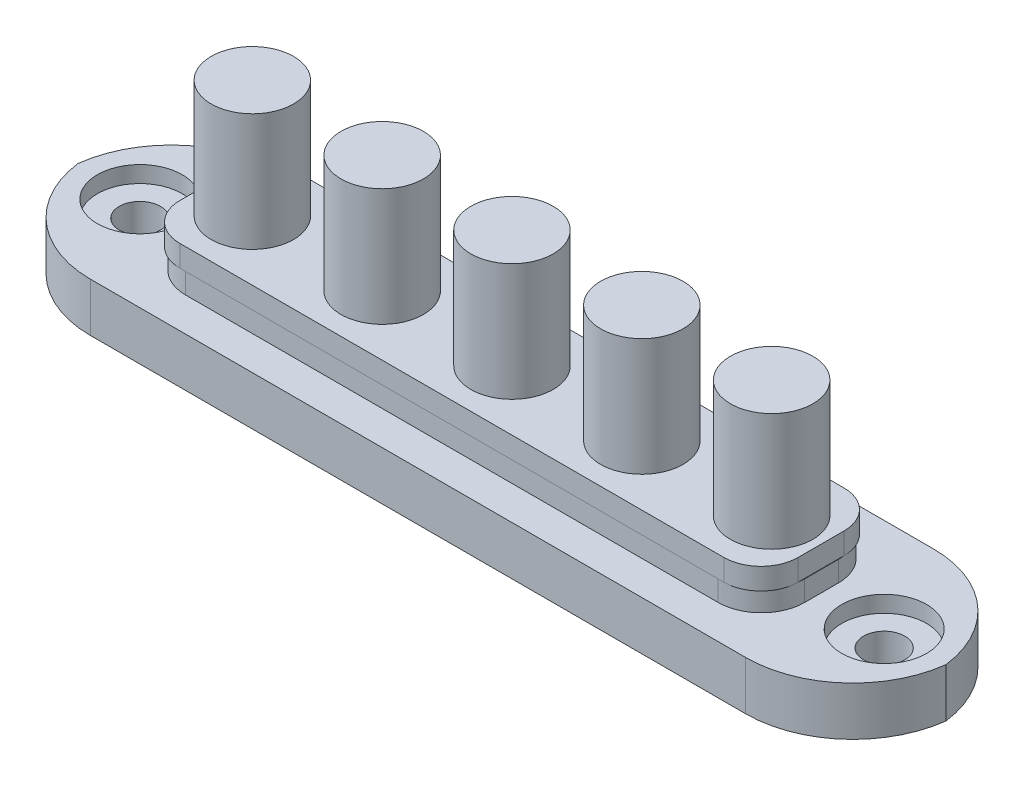
SolidWorks part; units mm, degrees
ref_plane "Front Plane" through (0, 0, 0) normal (0, 0, 1) x (1, 0, 0)
ref_plane "Top Plane" through (0, 0, 0) normal (0, 1, 0) x (1, 0, 0)
ref_plane "Right Plane" through (0, 0, 0) normal (1, 0, 0) x (0, 0, -1)
sketch "Sketch1" plane through (0, 0, 0) normal (0, 1, 0) x (1, 0, 0)
  line L1 (52.75, -11.4) -> (-52.75, -11.4)
  line L2 (52.75, -11.4) -> (52.75, 11.4)
  line L3 (52.75, 11.4) -> (-52.75, 11.4)
  line L4 (-52.75, -11.4) -> (-52.75, 11.4)
  line L5 (52.75, -11.4) -> (-52.75, 11.4) construction
  line L6 (52.75, 11.4) -> (-52.75, -11.4) construction
  point P0 (0, 0)
  dimension "D1" = 105.5
  dimension "D2" = 22.8
extrude "Boss-Extrude1" add sketch "Sketch1" along normal mid plane 5.92
fillet "Fillet1" radius 13 4 edges at (-52.75, 0, -11.4) (-52.75, 0, 11.4) (52.75, 0, -11.4) (52.75, 0, 11.4)
sketch "Sketch2" plane through (0, 2.96, 0) normal (0, 1, 0) x (1, 0, 0)
  circle A0 centre (-45.1512, 0) radius 2.5
  circle A1 centre (45.1512, 0) radius 2.5
  dimension "D1" = 5
  dimension "D4" = 5
  dimension "D2" = 7.5
  dimension "D3" = 7.5
extrude "Cut-Extrude1" cut sketch "Sketch2" against normal blind 5.92
sketch "Sketch3" plane through (0, 2.96, 0) normal (0, 1, 0) x (1, 0, 0)
  circle A0 centre (-45.1512, 0) radius 5.15
  circle A1 centre (45.1512, 0) radius 5.15
  dimension "D1" = 10.3
  dimension "D2" = 10.3
extrude "Cut-Extrude2" cut sketch "Sketch3" against normal blind 2
sketch "Sketch4" plane through (0, 2.96, 0) normal (0, 1, 0) x (1, 0, 0)
  line L1 (37.55, -7.29) -> (-37.55, -7.29)
  line L2 (37.55, -7.29) -> (37.55, 7.29)
  line L3 (37.55, 7.29) -> (-37.55, 7.29)
  line L4 (-37.55, -7.29) -> (-37.55, 7.29)
  line L5 (37.55, -7.29) -> (-37.55, 7.29) construction
  line L6 (37.55, 7.29) -> (-37.55, -7.29) construction
  point P0 (0, 0)
  dimension "D1" = 75.1
  dimension "D2" = 14.58
extrude "Boss-Extrude3" add sketch "Sketch4" along normal blind 2.48
fillet "Fillet2" radius 5.25 4 edges at (37.55, 4.2, 7.29) (37.55, 4.2, -7.29) (-37.55, 4.2, -7.29) (-37.55, 4.2, 7.29)
sketch "Sketch6" plane through (0, 5.44, 0) normal (0, 1, 0) x (1, 0, 0)
  line L1 (37.5, -7.295) -> (-37.5, -7.295)
  line L2 (37.5, -7.295) -> (37.5, 7.295)
  line L3 (37.5, 7.295) -> (-37.5, 7.295)
  line L4 (-37.5, -7.295) -> (-37.5, 7.295)
  line L5 (37.5, -7.295) -> (-37.5, 7.295) construction
  line L6 (37.5, 7.295) -> (-37.5, -7.295) construction
  point P0 (0, 0)
  dimension "D1" = 75
  dimension "D2" = 14.59
extrude "Boss-Extrude4" add sketch "Sketch6" along normal blind 2.6
fillet "Fillet4" radius 4.5 4 edges at (37.5, 6.74, -7.295) (37.5, 6.74, 7.295) (-37.5, 6.74, 7.295) (-37.5, 6.74, -7.295)
sketch "Sketch7" plane through (0, 8.04, 0) normal (0, 1, 0) x (1, 0, 0)
  circle A0 centre (-31.5, 0) radius 5
  circle A1 centre (-15.75, 0) radius 5
  circle A2 centre (0, 0) radius 5
  circle A3 centre (15.75, 0) radius 5
  circle A4 centre (31.5, 0) radius 5
  point P10 (32.0397, 0)
  point P11 (15.655, 0)
  point P12 (0, 0)
  point P14 (-16.4153, 0)
  point P15 (-32.368, 0)
  point P16 (32.2263, 0)
  point P17 (-31.895, 0)
  point P18 (31.9926, 0)
  point P21 (-35.254, 46.0797)
  dimension "D5" = 10
  dimension "D1" = 15.75
  dimension "D2" = 15.75
  dimension "D3" = 15.75
  dimension "D4" = 15.75
extrude "Boss-Extrude5" add sketch "Sketch7" along normal blind 14.25
